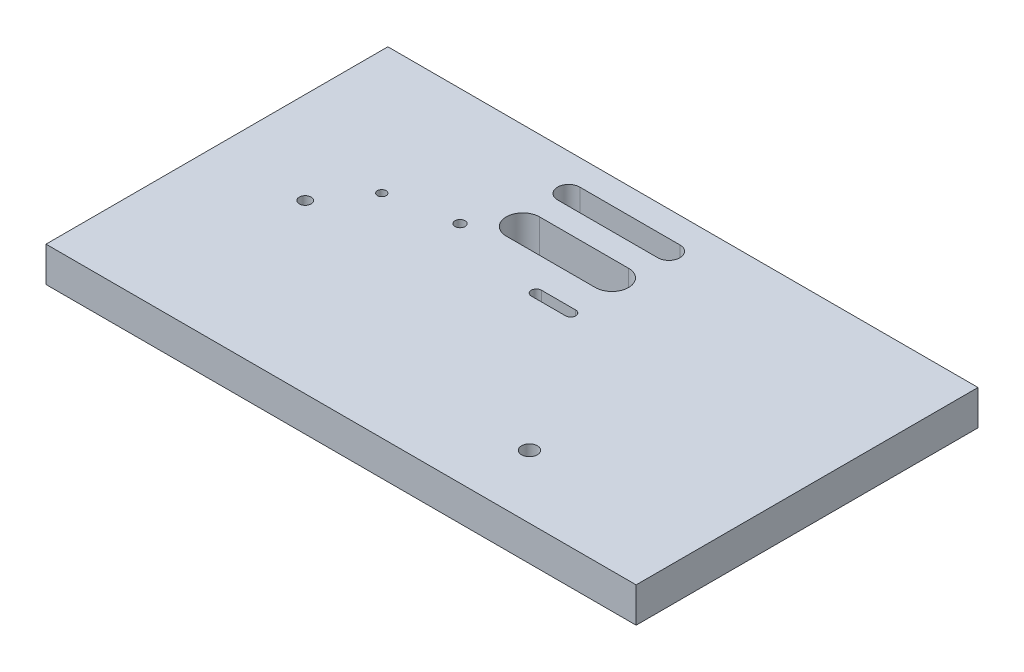
SolidWorks part; units mm, degrees
ref_plane "Front Plane" through (0, 0, 0) normal (0, 0, 1) x (1, 0, 0)
ref_plane "Top Plane" through (0, 0, 0) normal (0, 1, 0) x (1, 0, 0)
ref_plane "Right Plane" through (0, 0, 0) normal (1, 0, 0) x (0, 0, -1)
sketch "Sketch1" plane through (0, 0, 0) normal (0, 1, 0) x (1, 0, 0)
  line L1 (84.3608, 0) -> (-84.3608, 0)
  line L2 (84.3608, 0) -> (84.3608, 97.7396)
  line L3 (84.3608, 97.7396) -> (-84.3608, 97.7396)
  line L4 (-84.3608, 0) -> (-84.3608, 97.7396)
extrude "Boss-Extrude1" add sketch "Sketch1" along normal mid plane 10
hole_wizard "M3 Clearance Hole1" positions "3DSketch1" profile "Sketch2" hole size "M3" standard "ANSI Metric" end condition through all
sketch3d "3DSketch1"
  point P0 (-58.1139, 5, -47.855)
sketch "Sketch2" plane through (-58.1139, 5, -47.855) normal (1, 0, 0) x (0, 0, 1)
  line L0 (0, 0) -> (0, 10)
  line L1 (0, 10) -> (1.7, 10)
  line L2 (1.7, 10) -> (1.7, 0)
  line L5 (1.7, 0) -> (0, 0)
  line L11 (0, -6.35) -> (0, 107.95) construction
  dimension "Thru Hole Dia." = 3.4
  dimension "Thru Hole Depth" = 10
hole_wizard "Tap Drill for M3x0.5 Tap1" positions "Sketch4" profile "Sketch3" hole size "M3x0.5" standard "ANSI Metric" end condition through all
sketch "Sketch4" plane through (0, 5, 0) normal (0, 1, 0) x (1, 0, 0)
  point P0 (-48.9862, 60.6225)
sketch "Sketch3" plane through (-48.9862, 5, -60.6225) normal (1, 0, 0) x (0, 0, 1)
  line L0 (0, 0) -> (0, 10)
  line L1 (0, 10) -> (1.25, 10)
  line L2 (1.25, 10) -> (1.25, 0)
  line L5 (1.25, 0) -> (0, 0)
  line L11 (0, -6.35) -> (0, 107.95) construction
  dimension "Thru Hole Dia." = 2.5
  dimension "Thru Hole Depth" = 10
hole_wizard "M2.5 Clearance Hole1" positions "Sketch6" profile "Sketch5" hole size "M2.5" standard "ANSI Metric" end condition through all
sketch "Sketch6" plane through (0, 5, 0) normal (0, 1, 0) x (1, 0, 0)
  point P0 (-30.2474, 64.27)
sketch "Sketch5" plane through (-30.2474, 5, -64.27) normal (1, 0, 0) x (0, 0, 1)
  line L0 (0, 0) -> (0, 10)
  line L1 (0, 10) -> (1.45, 10)
  line L2 (1.45, 10) -> (1.45, 0)
  line L5 (1.45, 0) -> (0, 0)
  line L11 (0, -6.35) -> (0, 107.95) construction
  dimension "Thru Hole Dia." = 2.9
  dimension "Thru Hole Depth" = 10
hole_wizard "M4 Clearance Hole1" positions "Sketch8" profile "Sketch7" hole size "M4" standard "ANSI Metric"
sketch "Sketch8" plane through (0, 5, 0) normal (0, 1, 0) x (1, 0, 0)
  point P0 (35.7902, 18.0705)
sketch "Sketch7" plane through (35.7902, 5, -18.0705) normal (1, 0, 0) x (0, 0, 1)
  line L0 (0, 0) -> (0, 5.3519)
  line L1 (0, 5.3519) -> (2.25, 4)
  line L2 (2.25, 4) -> (2.25, 0)
  line L5 (2.25, 0) -> (0, 0)
  line L10 (0, 5.3519) -> (-2.25, 4) construction
  line L11 (0, -6.35) -> (0, 107.95) construction
  dimension "Hole Dia." = 4.5
  dimension "Hole Depth" = 4
  dimension "Drill Angle" = 118
hole_wizard "M2.5 Clearance Slot1" positions "Sketch10" profile "Sketch9" size "M2.5" standard "ANSI Metric" slot yes
sketch "Sketch10" plane through (0, 5, 0) normal (0, 1, 0) x (1, 0, 0)
  line L0 (-3.5859, 57.9698) -> (9.1141, 57.9698) construction
  point P0 (2.7641, 57.9698)
  dimension "D1" = 12.7
sketch "Sketch9" plane through (2.7641, 5, -57.9698) normal (1, 0, 0) x (0, 0, 1)
  line L0 (0, 0) -> (0, 10.8712)
  line L1 (0, 10.8712) -> (1.45, 10)
  line L2 (1.45, 10) -> (1.45, 0)
  line L5 (1.45, 0) -> (0, 0)
  line L10 (0, 10.8712) -> (-1.45, 10) construction
  line L11 (0, -6.35) -> (0, 107.95) construction
  dimension "Hole Dia." = 2.9
  dimension "Hole Depth" = 10
  dimension "Drill Angle" = 118
hole_wizard "3/8 (0.375) Clearance Dowel Slot1" positions "Sketch12" profile "Sketch11" size "3/8" standard "ANSI Inch" slot yes
sketch "Sketch12" plane through (0, 5, 0) normal (0, 1, 0) x (1, 0, 0)
  line L0 (-25.3352, 72.5459) -> (9.6648, 72.5459) construction
  point P0 (-7.8352, 72.5459)
  dimension "D1" = 35
sketch "Sketch11" plane through (-7.8352, 5, -72.5459) normal (1, 0, 0) x (0, 0, 1)
  line L0 (0, 0) -> (0, 12.8616)
  line L1 (0, 12.8616) -> (4.7625, 10)
  line L2 (4.7625, 10) -> (4.7625, 0)
  line L5 (4.7625, 0) -> (0, 0)
  line L10 (0, 12.8616) -> (-4.7625, 10) construction
  line L11 (0, -6.35) -> (0, 107.95) construction
  dimension "Hole Dia." = 9.525
  dimension "Hole Depth" = 10
  dimension "Drill Angle" = 118
hole_wizard "1/4 (0.25) Clearance Dowel Slot1" positions "Sketch14" profile "Sketch13" size "1/4" standard "ANSI Inch" slot yes
sketch "Sketch14" plane through (0, 5, 0) normal (0, 1, 0) x (1, 0, 0)
  line L0 (-25.362, 87.255) -> (9.638, 87.255) construction
  point P0 (-7.862, 87.255)
  dimension "D1" = 35
sketch "Sketch13" plane through (-7.862, 5, -87.255) normal (1, 0, 0) x (0, 0, 1)
  line L0 (0, 0) -> (0, 11.9077)
  line L1 (0, 11.9077) -> (3.175, 10)
  line L2 (3.175, 10) -> (3.175, 0)
  line L5 (3.175, 0) -> (0, 0)
  line L10 (0, 11.9077) -> (-3.175, 10) construction
  line L11 (0, -6.35) -> (0, 107.95) construction
  dimension "Hole Dia." = 6.35
  dimension "Hole Depth" = 10
  dimension "Drill Angle" = 118
